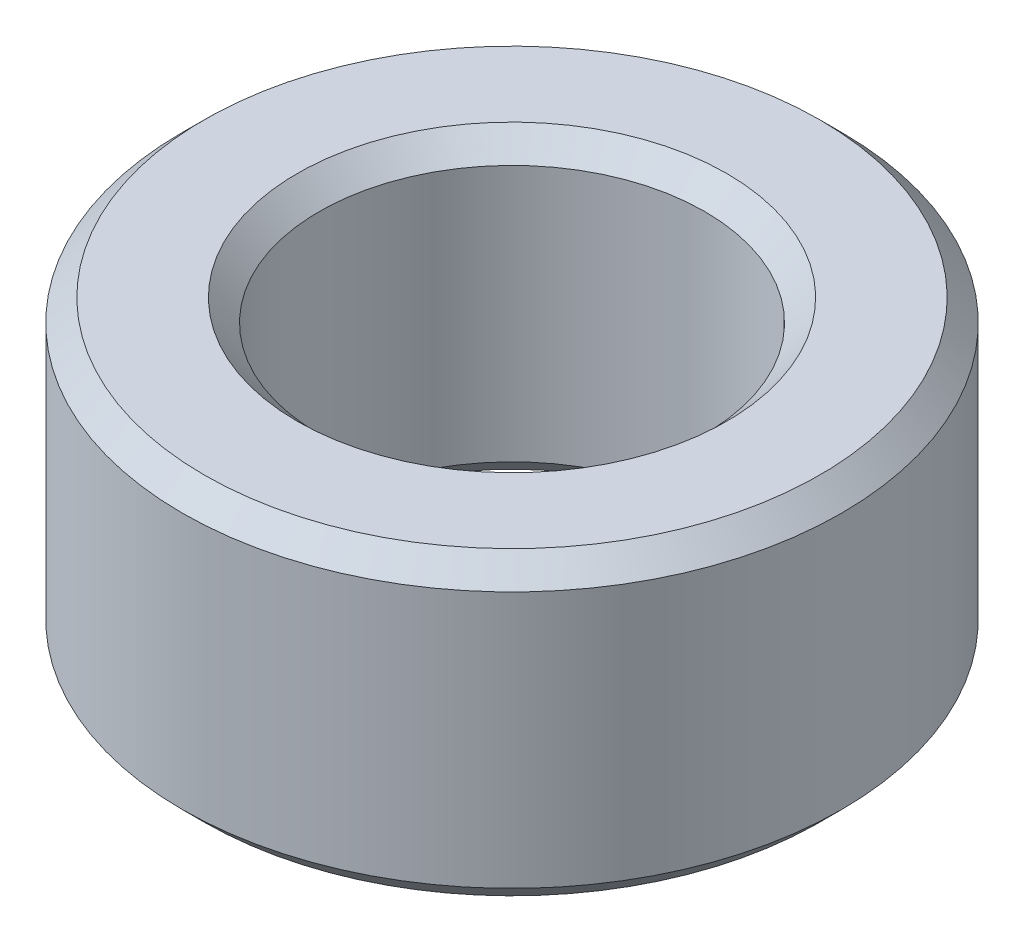
SolidWorks part; units mm, degrees
ref_plane "Front Plane" through (0, 0, 0) normal (0, 0, 1) x (1, 0, 0)
ref_plane "Top Plane" through (0, 0, 0) normal (0, 1, 0) x (1, 0, 0)
ref_plane "Right Plane" through (0, 0, 0) normal (1, 0, 0) x (0, 0, -1)
sketch "Sketch1" plane through (0, 0, 0) normal (0, 1, 0) x (1, 0, 0)
  circle A0 centre (0, 0) radius 30
  dimension "SLEEVE_OD" = 60
extrude "Boss-Extrude1" add sketch "Sketch1" along normal blind 27.3592
sketch "Sketch2" plane through (0, 0, 0) normal (0, 1, 0) x (1, 0, 0)
  circle A0 centre (0, 0) radius 17.537
  dimension "BORE_D" = 35.074
extrude "Cut-Extrude1" cut sketch "Sketch2" along normal through all
chamfer "Chamfer1" distance 2 angle 45 4 edges at (0, 27.3592, 17.537) (0, 0, 17.537) (0, 0, 30) (0, 27.3592, 30)
